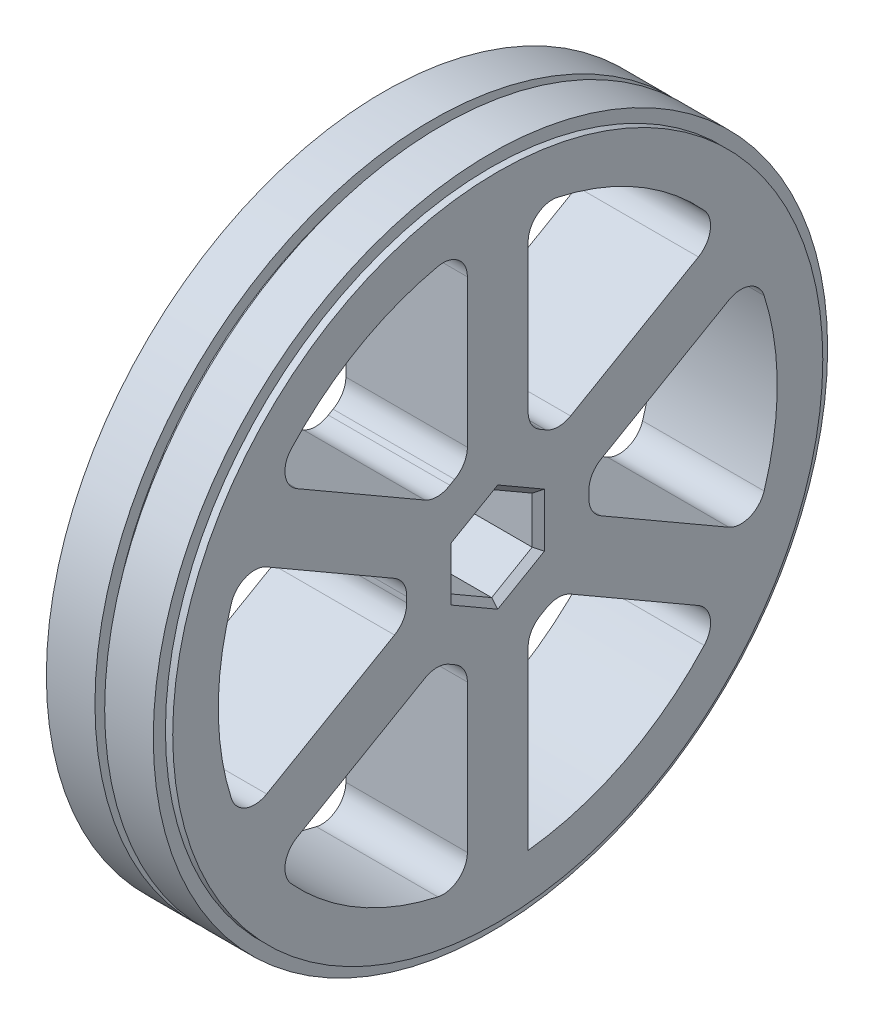
SolidWorks part; units mm, degrees
ref_plane "Front Plane" through (0, 0, 0) normal (0, 0, 1) x (1, 0, 0)
ref_plane "Top Plane" through (0, 0, 0) normal (0, 1, 0) x (1, 0, 0)
ref_plane "Right Plane" through (0, 0, 0) normal (1, 0, 0) x (0, 0, -1)
sketch "Axle Profile" plane through (0, 0, 0) normal (1, 0, 0) x (0, 0, -1)
  line L1 (0, -4.8895) -> (4.2344, -2.4448)
  line L2 (4.2344, -2.4448) -> (4.2344, 2.4447)
  line L3 (4.2344, 2.4447) -> (0, 4.8895)
  line L4 (0, 4.8895) -> (-4.2344, 2.4448)
  line L5 (-4.2344, 2.4448) -> (-4.2344, -2.4448)
  line L6 (-4.2344, -2.4448) -> (0, -4.8895)
  circle A0 centre (0, 0) radius 4.8895 construction
  circle A1 centre (0, 0) radius 9.525
  dimension "D1" = 9.779
  dimension ".625" = 19.05
extrude "Wheel Hub" add sketch "Axle Profile" along normal blind 12.7
fillet "Hub Fillet" [suppressed] radius 2.032
ref_plane "Spoke Plane" through (0, 0, -4.2344) normal (0, 0, 1) x (1, 0, 0)
sketch "Sketch2" plane through (0, 0, -4.2344) normal (0, 0, 1) x (1, 0, 0)
  line L0 (12.7, 2.4448) -> (0, -2.4447) construction
  line L1 (0, 2.4448) -> (12.7, -2.4447) construction
  circle A0 centre (6.35, 0) radius 2.54
  dimension "D1" = 5.08
extrude "Spoke" [suppressed] add sketch "Sketch2" against normal blind 25.4
ref_axis "Pattern Axis" through (12.7, 0, 0) along (-1, 0, 0)
pattern_circular "CirPattern1" [suppressed] count 6 over 360 about axis through (12.7, 0, 0) along (-1, 0, 0) of bodies 102
fillet "Hub/Spoke Fillet" [suppressed] radius 2.54
ref_plane "Mid Plane" through (6.35, 0, 0) normal (-1, 0, 0) x (0, 0, 1)
sketch "Sketch3" plane through (6.35, 0, 0) normal (-1, 0, 0) x (0, 0, 1)
  circle A0 centre (0, 0) radius 29.21
  circle A1 centre (0, 0) radius 33.9725
  dimension "D1" = 58.42
  dimension "D2" = 67.945
extrude "Wheel Rim" add sketch "Sketch3" along normal up to surface and the other way up to surface up to face at (0, 0, -9.525) other way up to face at (12.7, 0, -9.525)
fillet "Rim/Spoke Fillet" [suppressed] radius 2.54
fillet "Rim Fillet" [suppressed] radius 0.762
sketch "Sketch4" plane through (12.7, 0, 0) normal (1, 0, 0) x (0, 0, -1)
  line L0 (0, 8.9803) -> (0, 0) construction
  line L1 (-3.175, 8.9803) -> (3.175, 8.9803)
  line L2 (-3.175, 8.9803) -> (-3.175, 29.21)
  line L3 (-3.175, 29.21) -> (3.175, 29.21)
  line L4 (3.175, 8.9803) -> (3.175, 29.21)
  circle A0 centre (0, 0) radius 9.525 construction
  circle A1 centre (0, 0) radius 29.21 construction
  dimension "D1" = 6.35
extrude "Boss-Extrude1" add sketch "Sketch4" against normal up to surface (12.7 mm away) up to face at (0, 0, -29.21)
pattern_circular "Spokes" count 6 over 360 about axis through (0, 0, 0) along (1, 0, 0) of "Boss-Extrude1"
fillet "Spoke Fillets" radius 2.54 23 edges at (6.35, 8.9803, 3.175) (6.35, 7.2398, 6.1896) (6.35, -1.7405, 9.3646) (6.35, 1.7405, 9.3646) (6.35, -8.9803, 3.175) (6.35, -7.2398, 6.1896) (6.35, -8.9803, -3.175) (6.35, -7.2398, -6.1896) (6.35, -1.7405, -9.3646) (6.35, 1.7405, -9.3646) (6.35, 7.2398, -6.1896) (6.35, 8.9803, -3.175) (6.35, 29.0369, -3.175) (6.35, 29.0369, 3.175) (6.35, 17.2681, 23.5592) (6.35, 11.7688, 26.7342) (6.35, -11.7688, 26.7342) (6.35, -17.2681, 23.5592) (6.35, -29.0369, 3.175) (6.35, -17.2681, -23.5592) (6.35, -11.7688, -26.7342) (6.35, 11.7688, -26.7342) (6.35, 17.2681, -23.5592)
chamfer "Shaft Chamfers" distance 0.635 angle 45 12 edges at (0, 0, 4.2344) (0, 3.6671, 2.1172) (0, 3.6671, -2.1172) (0, 0, -4.2344) (0, -3.6671, -2.1172) (0, -3.6671, 2.1172) (12.7, -3.6671, -2.1172) (12.7, -3.6671, 2.1172) (12.7, 0, 4.2344) (12.7, 3.6671, 2.1172) (12.7, 3.6671, -2.1172) (12.7, 0, -4.2344)
ref_plane "Plane1" through (6.35, 0, 0) normal (-1, 0, 0) x (0, 0, 1)
sketch "Sketch6" plane through (6.35, 0, 0) normal (-1, 0, 0) x (0, 0, 1)
  circle A0 centre (0, 0) radius 33.9725
extrude "Extrude-Thin1" add sketch "Sketch6" along normal blind 5.08 from offset 0.508 separate body thin thin type one direction wall 1.27
mirror "Mirror1" about plane through (6.35, 0, 0) normal (-1, 0, 0) of bodies 107
